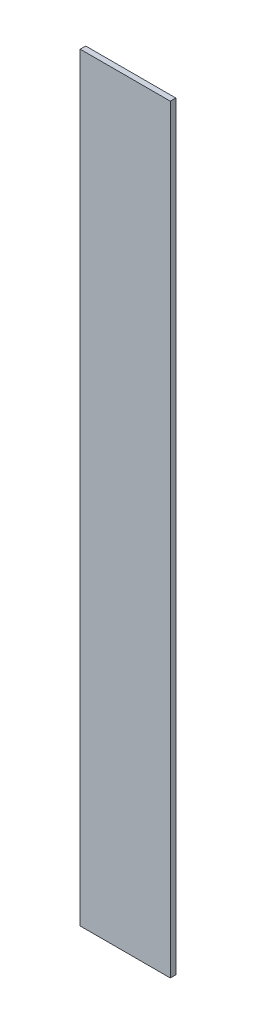
SolidWorks part; units mm, degrees
ref_plane "Front Plane" through (0, 0, 0) normal (0, 0, 1) x (1, 0, 0)
ref_plane "Top Plane" through (0, 0, 0) normal (0, 1, 0) x (1, 0, 0)
ref_plane "Right Plane" through (0, 0, 0) normal (1, 0, 0) x (0, 0, -1)
sketch "Sketch1" plane through (0, 0, 0) normal (0, 1, 0) x (1, 0, 0)
  line L0 (29.8232, 55.805) -> (29.6257, 52.8115) construction
  line L1 (-52.0023, 55.805) -> (29.8232, 55.805)
  line L2 (-52.0023, 55.805) -> (-52.0023, 50.805)
  line L3 (-52.0023, 50.805) -> (29.8232, 50.805)
  line L4 (29.8232, 55.805) -> (29.8232, 50.805)
  line L5 (-21.3075, -59.2094) -> (-69.6505, 114.0583) construction
  point P4 (42.5223, 17.6574)
  dimension "D2" = 5
extrude "Boss-Extrude1" add sketch "Sketch1" along normal blind 690.01
